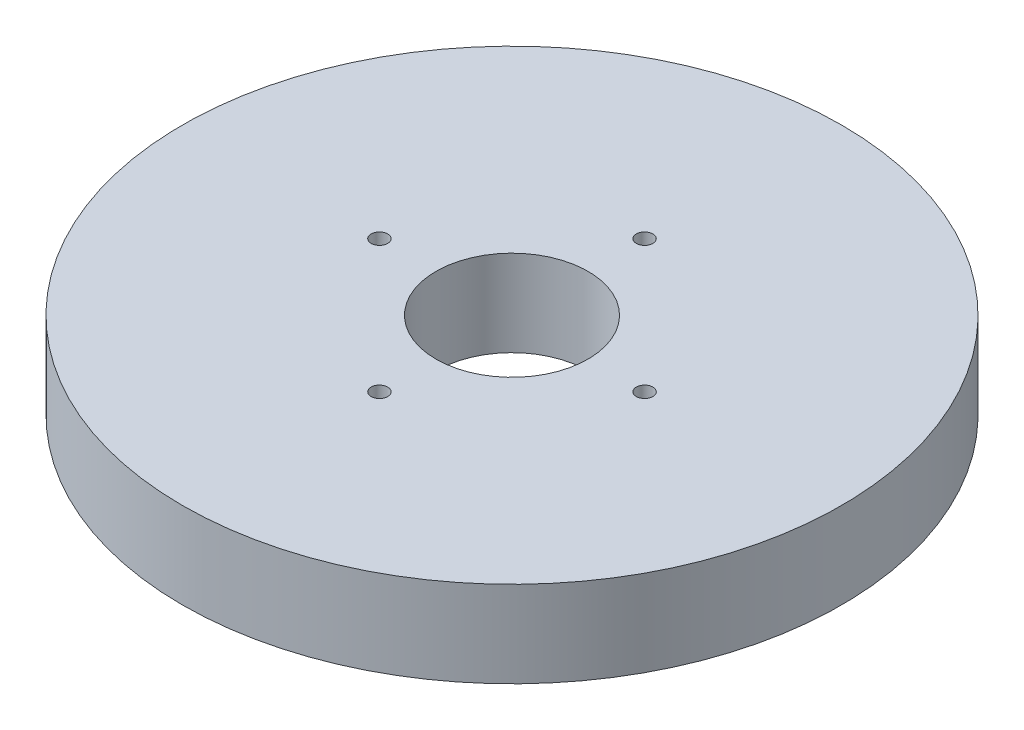
SolidWorks part; units mm, degrees
ref_plane "Front Plane" through (0, 0, 0) normal (0, 0, 1) x (1, 0, 0)
ref_plane "Top Plane" through (0, 0, 0) normal (0, 1, 0) x (1, 0, 0)
ref_plane "Right Plane" through (0, 0, 0) normal (1, 0, 0) x (0, 0, -1)
sketch "Sketch1" plane through (0, 0, 0) normal (0, 1, 0) x (1, 0, 0)
  circle A0 centre (0, 0) radius 65
  dimension "FLANGE_OD" = 130
extrude "Boss-Extrude1" add sketch "Sketch1" along normal blind 17
sketch "Sketch2" plane through (0, 0, 0) normal (0, 1, 0) x (1, 0, 0)
  circle A0 centre (0, 0) radius 15
  dimension "BORE_D" = 30
extrude "Cut-Extrude1" cut sketch "Sketch2" along normal through all
sketch "Sketch3" plane through (0, 17, 0) normal (0, 1, 0) x (1, 0, 0)
  circle A0 centre (0, 0) radius 26.1532 construction
  circle A1 centre (-26.1532, 0) radius 1.6309
  dimension "BOLT_D" = 3.2617
  dimension "BOLT_PCD" = 52.3063
extrude "Cut-Extrude2" cut sketch "Sketch3" against normal blind 11.0182
pattern_circular "CirPattern1" count 4 over 360 about axis through (0, 0, 0) along (0, 1, 0) of "Cut-Extrude2"
